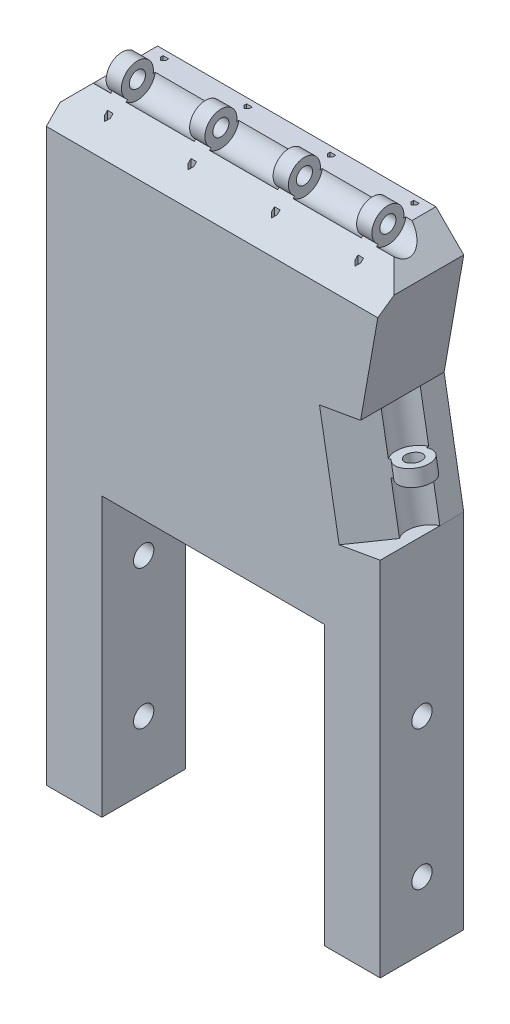
SolidWorks part; units mm, degrees
material "Custom Plastic"
ref_plane "Front Plane" through (0, 0, 0) normal (0, 0, 1) x (1, 0, 0)
ref_plane "Top Plane" through (0, 0, 0) normal (0, 1, 0) x (1, 0, 0)
ref_plane "Right Plane" through (0, 0, 0) normal (1, 0, 0) x (0, 0, -1)
sketch "Sketch1" plane through (0, 0, 0) normal (0, 0, 1) x (1, 0, 0)
  line L1 (-30, -30) -> (30, -30)
  line L2 (-30, -30) -> (-30, 30)
  line L3 (-30, 30) -> (30, 30)
  line L4 (30, -30) -> (30, 30)
  line L5 (-30, -30) -> (30, 30) construction
  line L6 (-30, 30) -> (30, -30) construction
  point P0 (0, 0)
  dimension "D1" = 60
  dimension "D2" = 60
extrude "Boss-Extrude1" add sketch "Sketch1" along normal mid plane 15
sketch "Sketch2" plane through (0, 0, 0) normal (0, 0, 1) x (1, 0, 0)
  line L0 (-30, 25) -> (-25, 30)
  line L1 (-30, 30) -> (-30, -30) construction
  line L2 (30, 30) -> (-30, 30) construction
  line L3 (-25, 30) -> (25, 30)
  line L4 (25, 30) -> (30, 25)
  line L5 (30, -30) -> (30, 30) construction
  line L10 (-30, -30) -> (30, -30) construction
  line L11 (14.5979, -30) -> (-15, -30)
  line L13 (-30, -15) -> (-30, 25)
  line L15 (-30, -15) -> (-30, -30)
  line L16 (-30, -30) -> (-15, -30)
  line L17 (14.5979, -30) -> (30, -30)
  line L18 (30, -30) -> (30, -15)
  line L19 (30, 25) -> (26.4735, 5)
  line L20 (26.4735, 5) -> (30, -15)
  point P6 (0, 0)
  dimension "D1" = 5
  dimension "D2" = 5
  dimension "D3" = 5
  dimension "D4" = 5
  dimension "D5" = 170
  dimension "D6" = 20
  dimension "D7" = 15
extrude "Cut-Extrude6" cut sketch "Sketch2" against normal through all both and the other way through all flip side to cut
ref_plane "Plane1" through (29.5, 0, 0) normal (1, 0, 0) x (0, 0, -1)
sketch "Sketch9" plane through (0, 0, 0) normal (1, 0, 0) x (0, 0, -1)
  line L0 (-7.5, 30) -> (0, 30)
  line L1 (7.5, 30) -> (-7.5, 30) construction
  line L7 (0, 30) -> (-7.5, 22.5)
  line L8 (-7.5, 5) -> (-7.5, 25) construction
  line L9 (-7.5, 22.5) -> (-7.5, 30)
  dimension "D1" = 45
  dimension "D2" = 7.5
extrude "Cut-Extrude7" cut sketch "Sketch9" against normal through all both and the other way through all
sketch "Sketch25" plane through (0, -30, 0) normal (0, -1, 0) x (1, 0, 0)
  line L0 (-30, 7.5) -> (30, 7.5) construction
  line L1 (-30, -7.5) -> (-20, -7.5)
  line L2 (-30, -7.5) -> (-30, 7.5)
  line L3 (-30, 7.5) -> (-20, 7.5)
  line L4 (-20, -7.5) -> (-20, 7.5)
  line L5 (-30, -7.5) -> (-20, 7.5) construction
  line L6 (-30, 7.5) -> (-20, -7.5) construction
  line L8 (0, -8.25) -> (0, 8.25) construction
  line L9 (30, 7.5) -> (20, 7.5)
  line L10 (20, -7.5) -> (20, 7.5)
  line L11 (30, -7.5) -> (20, -7.5)
  line L12 (30, -7.5) -> (30, 7.5)
  point P0 (-25, 0)
  dimension "D1" = 15
  dimension "D2" = 10
  dimension "D3" = 20
extrude "Boss-Extrude5" add sketch "Sketch25" along normal blind 50
sketch "Sketch26" plane through (-20, 0, 0) normal (1, 0, 0) x (0, 0, -1)
  line L5 (7.5, -80) -> (-7.5, -80) construction
  circle A0 centre (0, -68) radius 1.825
  circle A1 centre (0, -43) radius 1.825
  dimension "D1" = 3.65
  dimension "D2" = 3.65
  dimension "D3" = 12
  dimension "D4" = 25
extrude "Cut-Extrude22" cut sketch "Sketch26" against normal through all both and the other way through all
ref_plane "Plane4" through (-22.5, 0, 0) normal (-1, 0, 0) x (0, 0, 1)
sketch "Sketch28" plane through (-22.5, 0, 0) normal (-1, 0, 0) x (0, 0, 1)
  circle A0 centre (0, 30.5) radius 2.875
  dimension "D2" = 5.75
  dimension "D1" = 0.5
extrude "Boss-Extrude6" add sketch "Sketch28" along normal mid plane 2.75
pattern_linear "LPattern1" count 4 spacing 15 along (1, 0, 0) of "Boss-Extrude6"
sketch "Sketch29" plane through (-21.125, 0, 0) normal (1, 0, 0) x (0, 0, -1)
  circle A0 centre (0, 30.5) radius 3.25
  dimension "D1" = 6.5
extrude "Cut-Extrude23" cut sketch "Sketch29" along normal blind 12.25
mirror "Mirror1" about plane through (-22.5, 0, 0) normal (-1, 0, 0) of "Cut-Extrude23"
pattern_linear "LPattern2" count 4 spacing 15 along (1, 0, 0) of "Cut-Extrude23"
ref_plane "Plane5" through (1.7065, -9.678, 0) normal (-0.1736, 0.9848, 0) x (0.9848, 0.1736, 0)
sketch "Sketch31" plane through (1.7065, -9.678, 0) normal (-0.1736, 0.9848, 0) x (0.9848, 0.1736, 0)
  line L0 (26.9395, -7.5) -> (19.4395, -7.5)
  line L1 (19.4395, -7.5) -> (26.9395, 0)
  line L2 (26.9395, 0) -> (26.9395, -7.5)
  line L7 (26.9395, 7.5) -> (26.9395, -7.5) construction
  line L8 (26.9395, -7.5) -> (33.0172, -7.5) construction
  point P2 (34.115, -8.9976)
  dimension "D1" = 45
  dimension "D2" = 7.5
extrude "Cut-Extrude25" cut sketch "Sketch31" against normal up to vertex (10.1543 mm away) and the other way up to vertex (10.1543 mm away) up to point (30, -15, 7.5) other way up to point (26.4735, 5, -7.5)
sketch "Sketch32" plane through (1.7065, -9.678, 0) normal (-0.1736, 0.9848, 0) x (0.9848, 0.1736, 0)
  circle A0 centre (27.4395, 0) radius 2.875
  dimension "D2" = 5.75
  dimension "D1" = 0.5
extrude "Boss-Extrude7" add sketch "Sketch32" along normal mid plane 2.75
sketch "Sketch33" plane through (1.9453, -11.0321, 0) normal (0.1736, -0.9848, 0) x (0.9848, 0.1736, 0)
  circle A0 centre (27.4395, 0) radius 3.25
  dimension "D1" = 6.5
extrude "Cut-Extrude26" cut sketch "Sketch33" along normal up to vertex (8.7793 mm away) up to point (30, -15, 0)
mirror "Mirror2" about plane through (1.7065, -9.678, 0) normal (-0.1736, 0.9848, 0) of "Cut-Extrude26"
sketch "Sketch34" plane through (1.9453, -11.0321, 0) normal (0.1736, -0.9848, 0) x (0.9848, 0.1736, 0)
  circle A0 centre (27.4395, 0) radius 1.45
  dimension "D1" = 2.9
extrude "Cut-Extrude27" cut sketch "Sketch34" against normal up to surface (2.75 mm away) up to face at (27.6908, -3.7, -0.316)
sketch "Sketch35" plane through (23.875, 0, 0) normal (1, 0, 0) x (0, 0, -1)
  circle A0 centre (0, 30.5) radius 1.45
  dimension "D1" = 2.9
extrude "Cut-Extrude28" cut sketch "Sketch35" against normal up to surface (47.75 mm away) up to face at (-23.875, 29.6881, -0.316)
sketch "Sketch36" plane through (0, -30, 0) normal (0, -1, 0) x (1, 0, 0)
  line L0 (0, 6.5) -> (-2, 4.5)
  line L1 (-2, 4.5) -> (-2, 2.5)
  line L2 (-2, 2.5) -> (2, 2.5)
  line L3 (2, 2.5) -> (2, 4.5)
  line L4 (2, 4.5) -> (0, 6.5)
  line L5 (-20, 7.5) -> (20, 7.5) construction
  point P2 (0, 0)
  point P8 (0, 7.5)
  dimension "D1" = 2
  dimension "D2" = 135
  dimension "D3" = 2
  dimension "D4" = 135
  dimension "D5" = 4
  dimension "D6" = 1
extrude "Cut-Extrude29" cut sketch "Sketch36" against normal up to surface (30 mm away) up to plane "Top Plane"
pattern_linear "LPattern3" count 2 spacing 9 along (0, 0, -1) of "Cut-Extrude29"
sketch "Sketch41" plane through (0, 30, 0) normal (0, 1, 0) x (1, 0, 0)
  line L0 (-23, 6.5) -> (-22, 6.5)
  line L1 (-22, 6.5) -> (-22, 6)
  line L2 (-22, 6) -> (-22.5, 5.5)
  line L3 (-22.5, 8.25) -> (-22.5, -8.25) construction
  line L4 (-22.5, 5.5) -> (-23, 6)
  line L5 (-23, 6) -> (-23, 6.5)
  line L6 (25, 7.5) -> (-25, 7.5) construction
  line L7 (-8, 6) -> (-8, 6.5)
  line L8 (-8, 6.5) -> (-7, 6.5)
  line L9 (-7, 6.5) -> (-7, 6)
  line L10 (-7, 6) -> (-7.5, 5.5)
  line L11 (-7.5, 5.5) -> (-8, 6)
  line L12 (7, 6) -> (7, 6.5)
  line L13 (7, 6.5) -> (8, 6.5)
  line L14 (8, 6.5) -> (8, 6)
  line L15 (8, 6) -> (7.5, 5.5)
  line L16 (7.5, 5.5) -> (7, 6)
  line L17 (22, 6) -> (22, 6.5)
  line L18 (22, 6.5) -> (23, 6.5)
  line L19 (23, 6.5) -> (23, 6)
  line L20 (23, 6) -> (22.5, 5.5)
  line L21 (22.5, 5.5) -> (22, 6)
  line L22 (-8, -4) -> (-8, -3.5)
  line L23 (-8, -3.5) -> (-7, -3.5)
  line L24 (-7, -3.5) -> (-7, -4)
  line L25 (-7, -4) -> (-7.5, -4.5)
  line L26 (-7.5, -4.5) -> (-8, -4)
  line L27 (7, -4) -> (7, -3.5)
  line L28 (7, -3.5) -> (8, -3.5)
  line L29 (8, -3.5) -> (8, -4)
  line L30 (8, -4) -> (7.5, -4.5)
  line L31 (7.5, -4.5) -> (7, -4)
  line L32 (22, -4) -> (22, -3.5)
  line L33 (22, -3.5) -> (23, -3.5)
  line L34 (23, -3.5) -> (23, -4)
  line L35 (23, -4) -> (22.5, -4.5)
  line L36 (22.5, -4.5) -> (22, -4)
  line L37 (-23, -4) -> (-23, -3.5)
  line L38 (-23, -3.5) -> (-22, -3.5)
  line L39 (-22, -3.5) -> (-22, -4)
  line L40 (-22, -4) -> (-22.5, -4.5)
  line L41 (-22.5, -4.5) -> (-23, -4)
  dimension "D1" = 0.5
  dimension "D2" = 0.5
  dimension "D3" = 135
  dimension "D4" = 1
  dimension "D5" = 1
  dimension "D8" = 9
  dimension "D6" = 4
  dimension "D7" = 2
extrude "Cut-Extrude32" cut sketch "Sketch41" against normal blind 10
